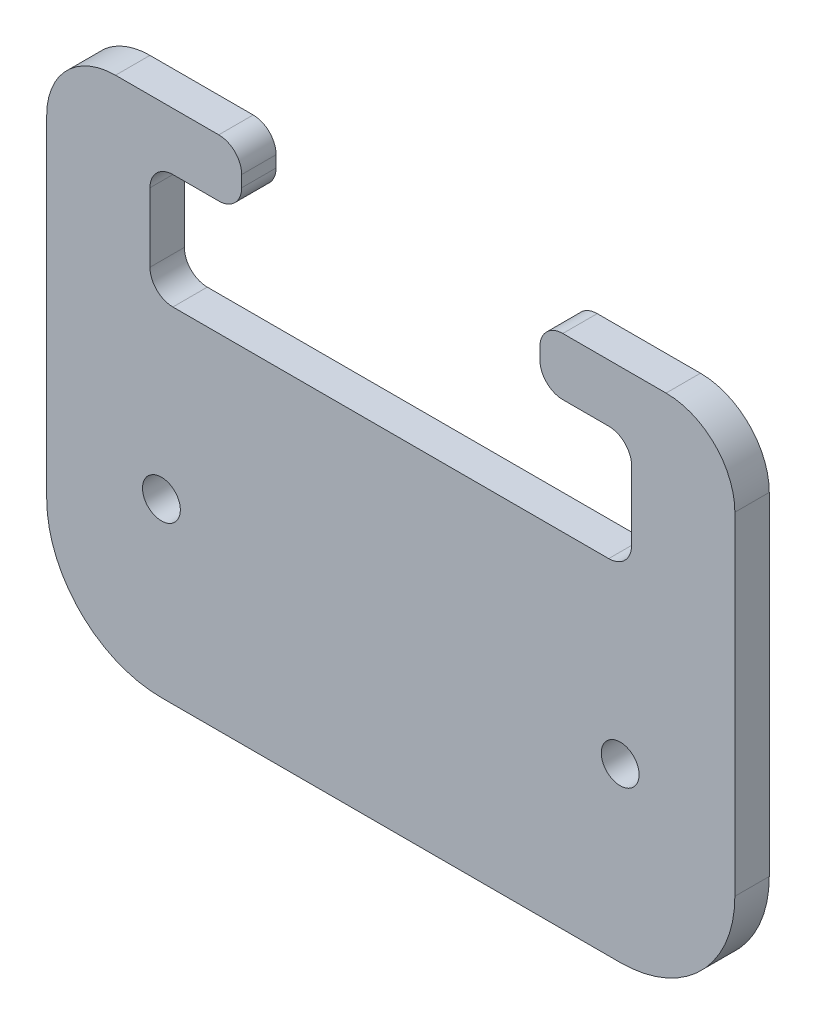
SolidWorks part; units mm, degrees
material "Thornel Mat VMA"
ref_plane "前视基准面" through (0, 0, 0) normal (0, 0, 1) x (1, 0, 0)
ref_plane "上视基准面" through (0, 0, 0) normal (0, 1, 0) x (1, 0, 0)
ref_plane "右视基准面" through (0, 0, 0) normal (1, 0, 0) x (0, 0, -1)
other "Configuration Table"
sketch "草图1" plane through (0, 0, 0) normal (0, 0, 1) x (1, 0, 0)
  line L0 (13, 22.5) -> (30, 22.5)
  line L1 (-30, 22.5) -> (-13, 22.5)
  line L2 (-30, 22.5) -> (-30, -22.5)
  line L3 (-30, -22.5) -> (30, -22.5)
  line L4 (30, 22.5) -> (30, -22.5)
  line L5 (-30, 22.5) -> (30, -22.5) construction
  line L6 (-30, -22.5) -> (30, 22.5) construction
  line L8 (13, 22.5) -> (13, 17.5)
  line L10 (-13, 22.5) -> (-13, 17.5)
  line L11 (21, 17.5) -> (13, 17.5)
  line L12 (21, 17.5) -> (21, 7.5)
  line L13 (21, 7.5) -> (-21, 7.5)
  line L14 (-21, 17.5) -> (-21, 7.5)
  line L15 (-13, 17.5) -> (-21, 17.5)
  point P0 (0, 0)
  dimension "D1" = 45
  dimension "D2" = 60
  dimension "D3" = 5
  dimension "D4" = 17
  dimension "D5" = 17
  dimension "D6" = 9
  dimension "D7" = 9
  dimension "D8" = 10
extrude "凸台-拉伸1" add sketch "草图1" along normal blind 3
fillet "圆角1" radius 6 2 edges at (30, 22.5, 1.5) (-30, 22.5, 1.5)
fillet "圆角2" radius 2 8 edges at (21, 17.5, 1.5) (21, 7.5, 1.5) (-21, 7.5, 1.5) (-21, 17.5, 1.5) (-13, 17.5, 1.5) (-13, 22.5, 1.5) (13, 17.5, 1.5) (13, 22.5, 1.5)
sketch "草图2" plane through (0, 0, 3) normal (0, 0, 1) x (1, 0, 0)
  line L0 (-30, -22.5) -> (30, -22.5) construction
  line L2 (0, 12.1144) -> (0, -26.36) construction
  circle A0 centre (-20, -7.5) radius 1.65
  circle A1 centre (20, -7.5) radius 1.65
  dimension "D1" = 3.3
  dimension "D2" = 3.3
  dimension "D6" = 20
  dimension "D3" = 15
  dimension "D4" = 15
  dimension "D5" = 40
extrude "切除-拉伸1" cut sketch "草图2" against normal blind 5
fillet "圆角3" radius 10 2 edges at (-30, -22.5, 1.5) (30, -22.5, 1.5)
